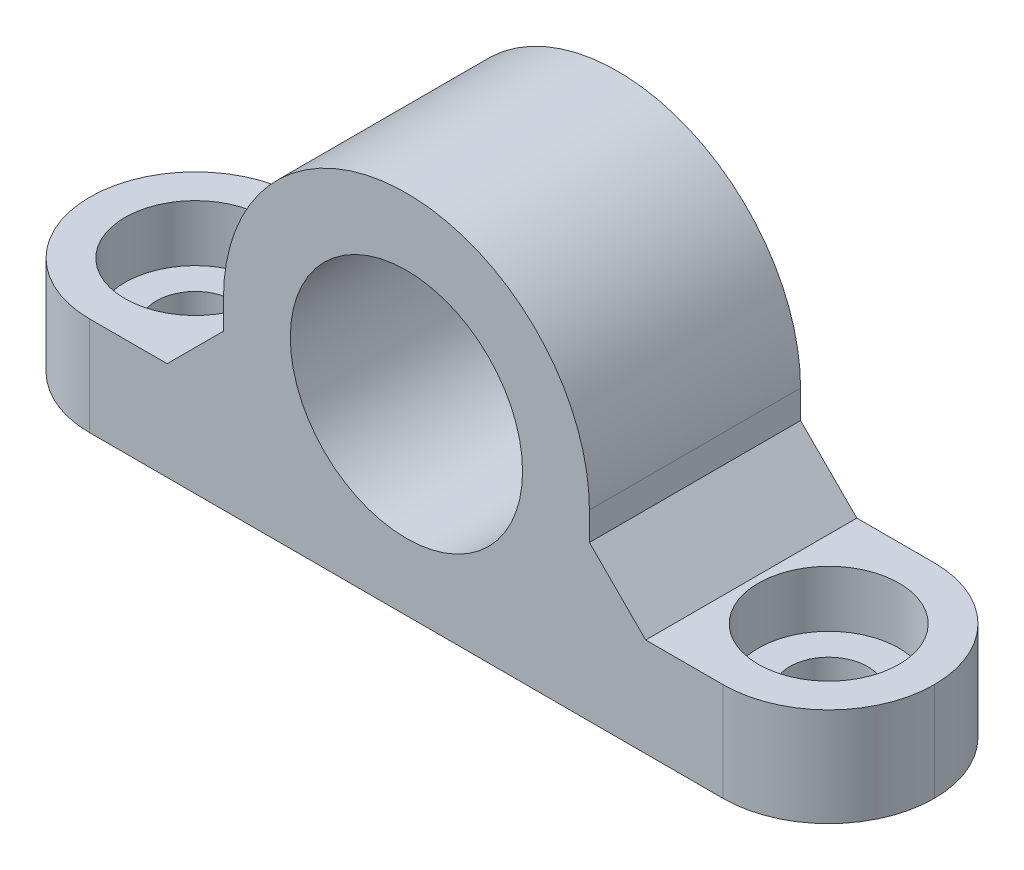
SolidWorks part; units mm, degrees
material "ABS"
ref_plane "Front Plane" through (0, 0, 0) normal (0, 0, 1) x (1, 0, 0)
ref_plane "Top Plane" through (0, 0, 0) normal (0, 1, 0) x (1, 0, 0)
ref_plane "Right Plane" through (0, 0, 0) normal (1, 0, 0) x (0, 0, -1)
sketch "Sketch1" plane through (0, 0, 0) normal (0, 1, 0) x (1, 0, 0)
  line L1 (-30, 7.5) -> (30, 7.5)
  line L2 (-30, 7.5) -> (-30, -7.5)
  line L3 (-30, -7.5) -> (30, -7.5)
  line L4 (30, 7.5) -> (30, -7.5)
  line L5 (-30, 7.5) -> (30, -7.5) construction
  line L6 (-30, -7.5) -> (30, 7.5) construction
  point P0 (0, 0)
  dimension "D1" = 15
  dimension "D2" = 60
extrude "Boss-Extrude1" add sketch "Sketch1" along normal blind 7
sketch "Sketch4" plane through (0, 0, 7.5) normal (0, 0, 1) x (1, 0, 0)
  line L0 (-30, 7) -> (30, 7) construction
  line L1 (-13, 13) -> (13, 13) construction
  line L2 (-13, 13) -> (-13, 7) construction
  line L3 (-13, 13) -> (-13, 7)
  line L4 (13, 13) -> (13, 7) construction
  line L5 (-13, 13) -> (13, 7) construction
  line L6 (-13, 7) -> (13, 13) construction
  line L7 (-30, 0) -> (30, 0) construction
  line L8 (-13, 7) -> (13, 7)
  line L9 (13, 7) -> (13, 13)
  arc A0 (-13, 13) -> (13, 13) centre (0, 13) cw
  point P0 (0, 10)
  point P9 (0, 0)
  dimension "D2" = 13
  dimension "D1" = 13
extrude "Boss-Extrude2" add sketch "Sketch4" against normal up to surface (15 mm away) up to face at (0, 3.5, -7.5)
chamfer "Chamfer1" distance 4 angle 45 2 edges
sketch "Sketch2" plane through (0, 7, 0) normal (0, 1, 0) x (1, 0, 0)
  line L0 (0, 0) -> (0, 16.1547) construction
  line L1 (30, 7.5) -> (17, 7.5) construction
  line L2 (-30, 7.5) -> (-30, -7.5) construction
  circle A0 centre (-22.5, 0) radius 2.75
  circle A1 centre (22.5, 0) radius 2.75
  dimension "D3" = 5.5
  dimension "D1" = 7.5
  dimension "D2" = 7.5
extrude "Cut-Extrude1" cut sketch "Sketch2" against normal through all
sketch "Sketch3" plane through (0, 7, 0) normal (0, 1, 0) x (1, 0, 0)
  line L0 (0, 0) -> (0, 12.9854) construction
  circle A0 centre (-22.5, 0) radius 5
  circle A1 centre (22.5, 0) radius 5
  dimension "D1" = 10
extrude "Cut-Extrude2" cut sketch "Sketch3" against normal offset from surface 3 and the other way through all up to face at (22.5, 0, -2.75)
sketch "Sketch6" plane through (0, 0, 7.5) normal (0, 0, 1) x (1, 0, 0)
  circle A0 centre (0, 13) radius 8.25
  arc A1 (13, 13) -> (-13, 13) centre (0, 13) ccw construction
  dimension "D1" = 16.5
extrude "Cut-Extrude4" cut sketch "Sketch6" against normal through all
fillet "Fillet2" radius 7.5 4 edges at (30, 3.5, 7.5) (30, 3.5, -7.5) (-30, 3.5, -7.5) (-30, 3.5, 7.5)
equation "\"D2@Sketch2\" = \"D1@Sketch2\""
equation "\"D1@Sketch4\" = \"D2@Sketch4\""
